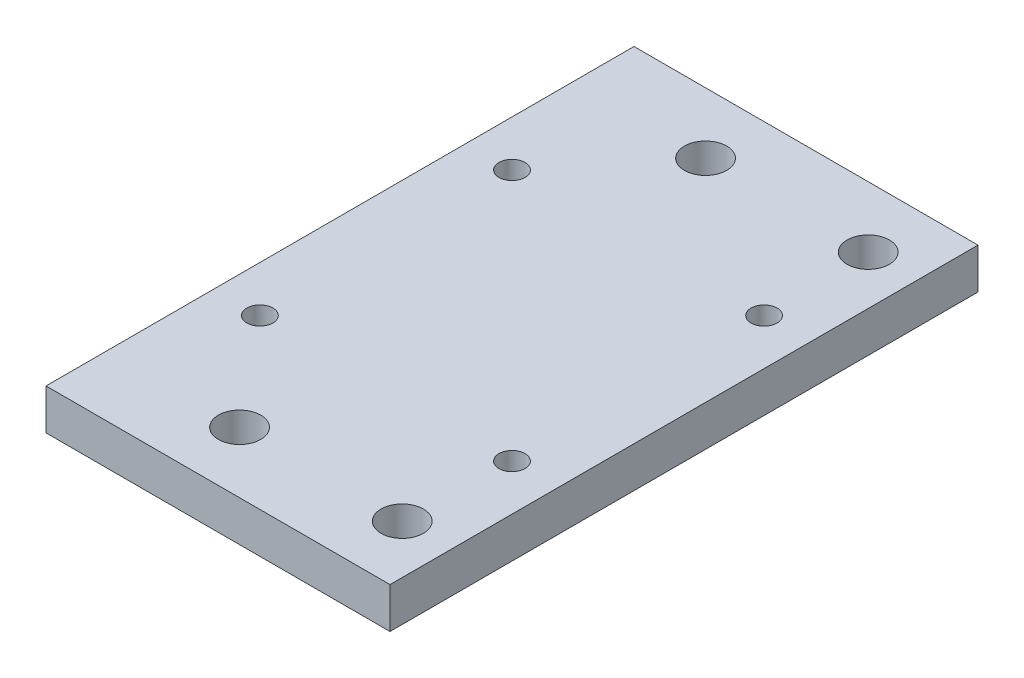
SolidWorks part; units mm, degrees
material "PET"
ref_plane "Front Plane" through (0, 0, 0) normal (0, 0, 1) x (1, 0, 0)
ref_plane "Top Plane" through (0, 0, 0) normal (0, 1, 0) x (1, 0, 0)
ref_plane "Right Plane" through (0, 0, 0) normal (1, 0, 0) x (0, 0, -1)
sketch "Sketch2" plane through (0, 0, 0) normal (0, 1, 0) x (1, 0, 0)
  line L0 (-21.15, 21.15) -> (21.15, -21.15) construction
  line L1 (-21.15, -21.15) -> (21.15, -21.15)
  line L2 (-21.15, -21.15) -> (-21.15, 21.15)
  line L3 (-21.15, 21.15) -> (21.15, 21.15)
  line L4 (21.15, -21.15) -> (21.15, 21.15)
  line L5 (-21.15, 21.15) -> (21.15, 21.15)
  line L6 (-21.15, 21.15) -> (-21.15, 36.15)
  line L7 (-21.15, 36.15) -> (21.15, 36.15)
  line L8 (21.15, 21.15) -> (21.15, 36.15)
  line L9 (21.15, -21.15) -> (-21.15, -21.15)
  line L10 (21.15, -21.15) -> (21.15, -36.15)
  line L11 (21.15, -36.15) -> (-21.15, -36.15)
  line L12 (-21.15, -21.15) -> (-21.15, -36.15)
  line L13 (-21.15, 28.65) -> (21.15, 28.65) construction
  line L14 (-21.15, -28.65) -> (21.15, -28.65) construction
  line L15 (15.5, 15.5) -> (-15.5, -15.5) construction
  circle A0 centre (-4.85, 28.65) radius 2.6
  circle A1 centre (15.15, 28.65) radius 2.6
  circle A2 centre (-4.85, -28.65) radius 2.6
  circle A3 centre (15.15, -28.65) radius 2.6
  circle A4 centre (-15.5, 15.5) radius 1.6
  circle A5 centre (15.5, -15.5) radius 1.6
  circle A6 centre (15.5, 15.5) radius 1.6
  circle A7 centre (-15.5, -15.5) radius 1.6
  dimension "D3" = 5.2
  dimension "D4" = 5.2
  dimension "D9" = 5.2
  dimension "D10" = 5.2
  dimension "D13" = 3.2
  dimension "D14" = 3.2
  dimension "D15" = 3.2
  dimension "D16" = 3.2
  dimension "D1" = 42.3
  dimension "D2" = 42.3
  dimension "D5" = 15
  dimension "D6" = 15
  dimension "D7" = 20
  dimension "D8" = 6
  dimension "D11" = 20
  dimension "D12" = 6
  dimension "D17" = 31
  dimension "D18" = 16.3
extrude "Boss-Extrude1" add sketch "Sketch2" along normal blind 5 contours L1 L4 L3 L2 A7 A6 A5 A4 | L1 L12 L11 L10 A3 A2 | L3 L8 L7 L6 A1 A0 region at (0, 0, 0) region at (-0.3695, 0, 28.65) region at (-0.3695, 0, -28.65)
sketch "Sketch3" [suppressed] plane through (0, 5, 0) normal (0, 1, 0) x (1, 0, 0)
  circle A0 centre (-15.5, 15.5) radius 3
  circle A1 centre (15.5, 15.5) radius 3
  circle A2 centre (15.5, -15.5) radius 3
  circle A3 centre (-15.5, -15.5) radius 3
  dimension "D1" = 6
  dimension "D2" = 6
  dimension "D3" = 6
  dimension "D4" = 6
extrude "Cut-Extrude1" [suppressed] cut sketch "Sketch3" against normal blind 3
